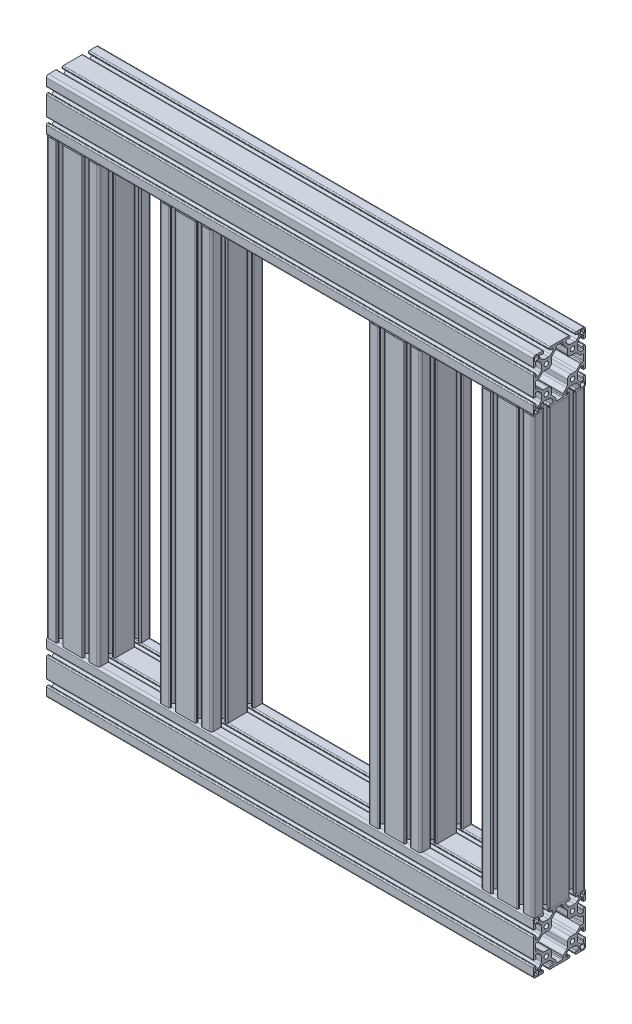
SolidWorks part; units mm, degrees
ref_plane "Front Plane" through (0, 0, 0) normal (0, 0, 1) x (1, 0, 0)
ref_plane "Top Plane" through (0, 0, 0) normal (0, 1, 0) x (1, 0, 0)
ref_plane "Right Plane" through (0, 0, 0) normal (1, 0, 0) x (0, 0, -1)
sketch "Sketch2" plane through (0, 0, 0) normal (0, 0, 1) x (1, 0, 0)
  line L0 (0, -372.5) -> (0, 372.5) construction
  line L1 (332.5, -372.5) -> (-332.5, -372.5)
  line L2 (332.5, -372.5) -> (332.5, 372.5)
  line L3 (332.5, 372.5) -> (-332.5, 372.5)
  line L4 (-332.5, -372.5) -> (-332.5, 372.5)
  line L5 (332.5, -372.5) -> (-332.5, 372.5) construction
  line L6 (332.5, 372.5) -> (-332.5, -372.5) construction
  line L7 (160, -372.5) -> (160, 372.5)
  line L8 (-160, -372.5) -> (-160, 372.5)
  point P0 (0, 0)
  dimension "D3" = 160
  dimension "D1" = 665
  dimension "D2" = 745
other "Aluminum 80X80(3)"
ref_plane "Plane2" through (332.5, 372.5, 0) normal (-1, 0, 0) x (0, -1, 0)
sketch "Sketch1" plane through (332.5, 372.5, 0) normal (-1, 0, 0) x (0, -1, 0)
  line L0 (33.22, -31.95) -> (37.715, -31.95)
  line L1 (38.35, -32.585) -> (38.35, -35.556)
  line L2 (35.556, -38.35) -> (32.585, -38.35)
  line L3 (31.95, -37.715) -> (31.95, -33.22)
  line L4 (-31.95, -33.22) -> (-31.95, -37.715)
  line L5 (-32.585, -38.35) -> (-35.556, -38.35)
  line L6 (-38.35, -35.556) -> (-38.35, -32.585)
  line L7 (-37.715, -31.95) -> (-33.22, -31.95)
  line L8 (-35.43, 5.41) -> (-32.7826, 5.41)
  line L9 (-31.8846, 5.782) -> (-26.7395, 10.9271)
  line L10 (-23.3809, 12.3182) -> (-17.0682, 12.3182)
  line L11 (-12.3182, 17.0682) -> (-12.3182, 23.3809)
  line L12 (-10.9271, 26.7395) -> (-5.782, 31.8846)
  line L13 (-5.41, 32.7826) -> (-5.41, 35.43)
  line L14 (-4.14, 36.7) -> (4.14, 36.7)
  line L15 (5.41, 35.43) -> (5.41, 32.7826)
  line L16 (5.782, 31.8846) -> (10.9271, 26.7395)
  line L17 (12.3182, 23.3809) -> (12.3182, 17.0682)
  line L18 (17.0682, 12.3182) -> (23.3809, 12.3182)
  line L19 (26.7395, 10.9271) -> (31.8846, 5.782)
  line L20 (32.7826, 5.41) -> (35.43, 5.41)
  line L21 (36.7, 4.14) -> (36.7, -4.14)
  line L22 (35.43, -5.41) -> (32.7826, -5.41)
  line L23 (31.8846, -5.782) -> (26.7395, -10.9271)
  line L24 (23.3809, -12.3182) -> (17.0682, -12.3182)
  line L25 (12.3182, -17.0682) -> (12.3182, -23.3809)
  line L26 (10.9271, -26.7395) -> (5.782, -31.8846)
  line L27 (5.41, -32.7826) -> (5.41, -35.43)
  line L28 (4.14, -36.7) -> (-4.14, -36.7)
  line L29 (-5.41, -35.43) -> (-5.41, -32.7826)
  line L30 (-5.782, -31.8846) -> (-10.9271, -26.7395)
  line L31 (-12.3182, -23.3809) -> (-12.3182, -17.0682)
  line L32 (-17.0682, -12.3182) -> (-23.3809, -12.3182)
  line L33 (-26.7395, -10.9271) -> (-31.8846, -5.782)
  line L34 (-32.7826, -5.41) -> (-35.43, -5.41)
  line L35 (-36.7, -4.14) -> (-36.7, 4.14)
  line L36 (-33.22, 31.95) -> (-37.715, 31.95)
  line L37 (-38.35, 32.585) -> (-38.35, 35.556)
  line L38 (-35.556, 38.35) -> (-32.585, 38.35)
  line L39 (-31.95, 37.715) -> (-31.95, 33.22)
  line L40 (31.95, 33.22) -> (31.95, 37.715)
  line L41 (32.585, 38.35) -> (35.556, 38.35)
  line L42 (38.35, 35.556) -> (38.35, 32.585)
  line L43 (37.715, 31.95) -> (33.22, 31.95)
  line L44 (-40, 14.37) -> (-40, -14.37)
  line L45 (-38.43, -15.94) -> (-37.51, -15.94)
  line L46 (-35.94, -14.37) -> (-35.94, -13.15)
  line L47 (-35.94, -13.15) -> (-36.7, -13.15)
  line L48 (-36.7, -13.15) -> (-36.7, -10.985)
  line L49 (-35.43, -9.715) -> (-32.9871, -9.715)
  line L50 (-32.3578, -9.9757) -> (-29.1593, -13.1742)
  line L51 (-27.6822, -16.6166) -> (-27.6822, -23.3834)
  line L52 (-29.1593, -26.8258) -> (-32.3578, -30.0243)
  line L53 (-32.9871, -30.285) -> (-35.43, -30.285)
  line L54 (-36.7, -29.015) -> (-36.7, -26.85)
  line L55 (-36.7, -26.85) -> (-35.94, -26.85)
  line L56 (-35.94, -26.85) -> (-35.94, -25.63)
  line L57 (-37.51, -24.06) -> (-38.43, -24.06)
  line L58 (-40, -25.63) -> (-40, -36.82)
  line L59 (-36.82, -40) -> (-25.63, -40)
  line L60 (-24.06, -38.43) -> (-24.06, -37.51)
  line L61 (-25.63, -35.94) -> (-26.85, -35.94)
  line L62 (-26.85, -35.94) -> (-26.85, -36.7)
  line L63 (-26.85, -36.7) -> (-29.015, -36.7)
  line L64 (-30.285, -35.43) -> (-30.285, -32.9871)
  line L65 (-30.0243, -32.3578) -> (-26.8258, -29.1593)
  line L66 (-23.3834, -27.6822) -> (-16.6166, -27.6822)
  line L67 (-13.1742, -29.1593) -> (-9.9757, -32.3578)
  line L68 (-9.715, -32.9871) -> (-9.715, -35.43)
  line L69 (-10.985, -36.7) -> (-13.15, -36.7)
  line L70 (-13.15, -36.7) -> (-13.15, -35.94)
  line L71 (-13.15, -35.94) -> (-14.37, -35.94)
  line L72 (-15.94, -37.51) -> (-15.94, -38.43)
  line L73 (-14.37, -40) -> (14.37, -40)
  line L74 (15.94, -38.43) -> (15.94, -37.51)
  line L75 (14.37, -35.94) -> (13.15, -35.94)
  line L76 (13.15, -35.94) -> (13.15, -36.7)
  line L77 (13.15, -36.7) -> (10.985, -36.7)
  line L78 (9.715, -35.43) -> (9.715, -32.9871)
  line L79 (9.9757, -32.3578) -> (13.1742, -29.1593)
  line L80 (16.6166, -27.6822) -> (23.3834, -27.6822)
  line L81 (26.8258, -29.1593) -> (30.0243, -32.3578)
  line L82 (30.285, -32.9871) -> (30.285, -35.43)
  line L83 (29.015, -36.7) -> (26.85, -36.7)
  line L84 (26.85, -36.7) -> (26.85, -35.94)
  line L85 (26.85, -35.94) -> (25.63, -35.94)
  line L86 (24.06, -37.51) -> (24.06, -38.43)
  line L87 (25.63, -40) -> (36.82, -40)
  line L88 (40, -36.82) -> (40, -25.63)
  line L89 (38.43, -24.06) -> (37.51, -24.06)
  line L90 (35.94, -25.63) -> (35.94, -26.85)
  line L91 (35.94, -26.85) -> (36.7, -26.85)
  line L92 (36.7, -26.85) -> (36.7, -29.015)
  line L93 (35.43, -30.285) -> (32.9871, -30.285)
  line L94 (32.3578, -30.0243) -> (29.1593, -26.8258)
  line L95 (27.6822, -23.3834) -> (27.6822, -16.6166)
  line L96 (29.1593, -13.1742) -> (32.3578, -9.9757)
  line L97 (32.9871, -9.715) -> (35.43, -9.715)
  line L98 (36.7, -10.985) -> (36.7, -13.15)
  line L99 (36.7, -13.15) -> (35.94, -13.15)
  line L100 (35.94, -13.15) -> (35.94, -14.37)
  line L101 (37.51, -15.94) -> (38.43, -15.94)
  line L102 (40, -14.37) -> (40, 14.37)
  line L103 (38.43, 15.94) -> (37.51, 15.94)
  line L104 (35.94, 14.37) -> (35.94, 13.15)
  line L105 (35.94, 13.15) -> (36.7, 13.15)
  line L106 (36.7, 13.15) -> (36.7, 10.985)
  line L107 (35.43, 9.715) -> (32.9871, 9.715)
  line L108 (32.3578, 9.9757) -> (29.1593, 13.1742)
  line L109 (27.6822, 16.6166) -> (27.6822, 23.3834)
  line L110 (29.1593, 26.8258) -> (32.3578, 30.0243)
  line L111 (32.9871, 30.285) -> (35.43, 30.285)
  line L112 (36.7, 29.015) -> (36.7, 26.85)
  line L113 (36.7, 26.85) -> (35.94, 26.85)
  line L114 (35.94, 26.85) -> (35.94, 25.63)
  line L115 (37.51, 24.06) -> (38.43, 24.06)
  line L116 (40, 25.63) -> (40, 36.82)
  line L117 (36.82, 40) -> (25.63, 40)
  line L118 (24.06, 38.43) -> (24.06, 37.51)
  line L119 (25.63, 35.94) -> (26.85, 35.94)
  line L120 (26.85, 35.94) -> (26.85, 36.7)
  line L121 (26.85, 36.7) -> (29.015, 36.7)
  line L122 (30.285, 35.43) -> (30.285, 32.9871)
  line L123 (30.0243, 32.3578) -> (26.8258, 29.1593)
  line L124 (23.3834, 27.6822) -> (16.6166, 27.6822)
  line L125 (13.1742, 29.1593) -> (9.9757, 32.3578)
  line L126 (9.715, 32.9871) -> (9.715, 35.43)
  line L127 (10.985, 36.7) -> (13.15, 36.7)
  line L128 (13.15, 36.7) -> (13.15, 35.94)
  line L129 (13.15, 35.94) -> (14.37, 35.94)
  line L130 (15.94, 37.51) -> (15.94, 38.43)
  line L131 (14.37, 40) -> (-14.37, 40)
  line L132 (-15.94, 38.43) -> (-15.94, 37.51)
  line L133 (-14.37, 35.94) -> (-13.15, 35.94)
  line L134 (-13.15, 35.94) -> (-13.15, 36.7)
  line L135 (-13.15, 36.7) -> (-10.985, 36.7)
  line L136 (-9.715, 35.43) -> (-9.715, 32.9871)
  line L137 (-9.9757, 32.3578) -> (-13.1742, 29.1593)
  line L138 (-16.6166, 27.6822) -> (-23.3834, 27.6822)
  line L139 (-26.8258, 29.1593) -> (-30.0243, 32.3578)
  line L140 (-30.285, 32.9871) -> (-30.285, 35.43)
  line L141 (-29.015, 36.7) -> (-26.85, 36.7)
  line L142 (-26.85, 36.7) -> (-26.85, 35.94)
  line L143 (-26.85, 35.94) -> (-25.63, 35.94)
  line L144 (-24.06, 37.51) -> (-24.06, 38.43)
  line L145 (-25.63, 40) -> (-36.82, 40)
  line L146 (-40, 36.82) -> (-40, 25.63)
  line L147 (-38.43, 24.06) -> (-37.51, 24.06)
  line L148 (-35.94, 25.63) -> (-35.94, 26.85)
  line L149 (-35.94, 26.85) -> (-36.7, 26.85)
  line L150 (-36.7, 26.85) -> (-36.7, 29.015)
  line L151 (-35.43, 30.285) -> (-32.9871, 30.285)
  line L152 (-32.3578, 30.0243) -> (-29.1593, 26.8258)
  line L153 (-27.6822, 23.3834) -> (-27.6822, 16.6166)
  line L154 (-29.1593, 13.1742) -> (-32.3578, 9.9757)
  line L155 (-32.9871, 9.715) -> (-35.43, 9.715)
  line L156 (-36.7, 10.985) -> (-36.7, 13.15)
  line L157 (-36.7, 13.15) -> (-35.94, 13.15)
  line L158 (-35.94, 13.15) -> (-35.94, 14.37)
  line L159 (-37.51, 15.94) -> (-38.43, 15.94)
  arc A0 (33.22, -31.95) -> (31.95, -33.22) centre (33.22, -33.22) ccw
  arc A1 (38.35, -32.585) -> (37.715, -31.95) centre (37.715, -32.585) ccw
  arc A2 (35.556, -38.35) -> (38.35, -35.556) centre (35.556, -35.556) ccw
  arc A3 (31.95, -37.715) -> (32.585, -38.35) centre (32.585, -37.715) ccw
  arc A4 (-31.95, -33.22) -> (-33.22, -31.95) centre (-33.22, -33.22) ccw
  arc A5 (-32.585, -38.35) -> (-31.95, -37.715) centre (-32.585, -37.715) ccw
  arc A6 (-38.35, -35.556) -> (-35.556, -38.35) centre (-35.556, -35.556) ccw
  arc A7 (-37.715, -31.95) -> (-38.35, -32.585) centre (-37.715, -32.585) ccw
  arc A8 (-35.43, 5.41) -> (-36.7, 4.14) centre (-35.43, 4.14) ccw
  arc A9 (-32.7826, 5.41) -> (-31.8846, 5.782) centre (-32.7826, 6.68) ccw
  arc A10 (-23.3809, 12.3182) -> (-26.7395, 10.9271) centre (-23.3809, 7.5684) ccw
  arc A11 (-17.0682, 12.3182) -> (-12.3182, 17.0682) centre (-17.0682, 17.0682) ccw
  arc A12 (-10.9271, 26.7395) -> (-12.3182, 23.3809) centre (-7.5684, 23.3809) ccw
  arc A13 (-5.782, 31.8846) -> (-5.41, 32.7826) centre (-6.68, 32.7826) ccw
  arc A14 (-4.14, 36.7) -> (-5.41, 35.43) centre (-4.14, 35.43) ccw
  arc A15 (5.41, 35.43) -> (4.14, 36.7) centre (4.14, 35.43) ccw
  arc A16 (5.41, 32.7826) -> (5.782, 31.8846) centre (6.68, 32.7826) ccw
  arc A17 (12.3182, 23.3809) -> (10.9271, 26.7395) centre (7.5684, 23.3809) ccw
  arc A18 (12.3182, 17.0682) -> (17.0682, 12.3182) centre (17.0682, 17.0682) ccw
  arc A19 (26.7395, 10.9271) -> (23.3809, 12.3182) centre (23.3809, 7.5684) ccw
  arc A20 (31.8846, 5.782) -> (32.7826, 5.41) centre (32.7826, 6.68) ccw
  arc A21 (36.7, 4.14) -> (35.43, 5.41) centre (35.43, 4.14) ccw
  arc A22 (35.43, -5.41) -> (36.7, -4.14) centre (35.43, -4.14) ccw
  arc A23 (32.7826, -5.41) -> (31.8846, -5.782) centre (32.7826, -6.68) ccw
  arc A24 (23.3809, -12.3182) -> (26.7395, -10.9271) centre (23.3809, -7.5684) ccw
  arc A25 (17.0682, -12.3182) -> (12.3182, -17.0682) centre (17.0682, -17.0682) ccw
  arc A26 (10.9271, -26.7395) -> (12.3182, -23.3809) centre (7.5684, -23.3809) ccw
  arc A27 (5.782, -31.8846) -> (5.41, -32.7826) centre (6.68, -32.7826) ccw
  arc A28 (4.14, -36.7) -> (5.41, -35.43) centre (4.14, -35.43) ccw
  arc A29 (-5.41, -35.43) -> (-4.14, -36.7) centre (-4.14, -35.43) ccw
  arc A30 (-5.41, -32.7826) -> (-5.782, -31.8846) centre (-6.68, -32.7826) ccw
  arc A31 (-12.3182, -23.3809) -> (-10.9271, -26.7395) centre (-7.5684, -23.3809) ccw
  arc A32 (-12.3182, -17.0682) -> (-17.0682, -12.3182) centre (-17.0682, -17.0682) ccw
  arc A33 (-26.7395, -10.9271) -> (-23.3809, -12.3182) centre (-23.3809, -7.5684) ccw
  arc A34 (-31.8846, -5.782) -> (-32.7826, -5.41) centre (-32.7826, -6.68) ccw
  arc A35 (-36.7, -4.14) -> (-35.43, -5.41) centre (-35.43, -4.14) ccw
  circle A36 centre (20, -20) radius 3.405
  circle A37 centre (-20, -20) radius 3.405
  circle A38 centre (-20, 20) radius 3.405
  circle A39 centre (20, 20) radius 3.405
  arc A40 (-33.22, 31.95) -> (-31.95, 33.22) centre (-33.22, 33.22) ccw
  arc A41 (-38.35, 32.585) -> (-37.715, 31.95) centre (-37.715, 32.585) ccw
  arc A42 (-35.556, 38.35) -> (-38.35, 35.556) centre (-35.556, 35.556) ccw
  arc A43 (-31.95, 37.715) -> (-32.585, 38.35) centre (-32.585, 37.715) ccw
  arc A44 (31.95, 33.22) -> (33.22, 31.95) centre (33.22, 33.22) ccw
  arc A45 (32.585, 38.35) -> (31.95, 37.715) centre (32.585, 37.715) ccw
  arc A46 (38.35, 35.556) -> (35.556, 38.35) centre (35.556, 35.556) ccw
  arc A47 (37.715, 31.95) -> (38.35, 32.585) centre (37.715, 32.585) ccw
  arc A48 (-38.43, 15.94) -> (-40, 14.37) centre (-38.43, 14.37) ccw
  arc A49 (-40, -14.37) -> (-38.43, -15.94) centre (-38.43, -14.37) ccw
  arc A50 (-37.51, -15.94) -> (-35.94, -14.37) centre (-37.51, -14.37) ccw
  arc A51 (-35.43, -9.715) -> (-36.7, -10.985) centre (-35.43, -10.985) ccw
  arc A52 (-32.3578, -9.9757) -> (-32.9871, -9.715) centre (-32.9871, -10.605) ccw
  arc A53 (-27.6822, -16.6166) -> (-29.1593, -13.1742) centre (-32.4322, -16.6166) ccw
  arc A54 (-29.1593, -26.8258) -> (-27.6822, -23.3834) centre (-32.4322, -23.3834) ccw
  arc A55 (-32.9871, -30.285) -> (-32.3578, -30.0243) centre (-32.9871, -29.395) ccw
  arc A56 (-36.7, -29.015) -> (-35.43, -30.285) centre (-35.43, -29.015) ccw
  arc A57 (-35.94, -25.63) -> (-37.51, -24.06) centre (-37.51, -25.63) ccw
  arc A58 (-38.43, -24.06) -> (-40, -25.63) centre (-38.43, -25.63) ccw
  arc A59 (-40, -36.82) -> (-36.82, -40) centre (-36.82, -36.82) ccw
  arc A60 (-25.63, -40) -> (-24.06, -38.43) centre (-25.63, -38.43) ccw
  arc A61 (-24.06, -37.51) -> (-25.63, -35.94) centre (-25.63, -37.51) ccw
  arc A62 (-30.285, -35.43) -> (-29.015, -36.7) centre (-29.015, -35.43) ccw
  arc A63 (-30.0243, -32.3578) -> (-30.285, -32.9871) centre (-29.395, -32.9871) ccw
  arc A64 (-23.3834, -27.6822) -> (-26.8258, -29.1593) centre (-23.3834, -32.4322) ccw
  arc A65 (-13.1742, -29.1593) -> (-16.6166, -27.6822) centre (-16.6166, -32.4322) ccw
  arc A66 (-9.715, -32.9871) -> (-9.9757, -32.3578) centre (-10.605, -32.9871) ccw
  arc A67 (-10.985, -36.7) -> (-9.715, -35.43) centre (-10.985, -35.43) ccw
  arc A68 (-14.37, -35.94) -> (-15.94, -37.51) centre (-14.37, -37.51) ccw
  arc A69 (-15.94, -38.43) -> (-14.37, -40) centre (-14.37, -38.43) ccw
  arc A70 (14.37, -40) -> (15.94, -38.43) centre (14.37, -38.43) ccw
  arc A71 (15.94, -37.51) -> (14.37, -35.94) centre (14.37, -37.51) ccw
  arc A72 (9.715, -35.43) -> (10.985, -36.7) centre (10.985, -35.43) ccw
  arc A73 (9.9757, -32.3578) -> (9.715, -32.9871) centre (10.605, -32.9871) ccw
  arc A74 (16.6166, -27.6822) -> (13.1742, -29.1593) centre (16.6166, -32.4322) ccw
  arc A75 (26.8258, -29.1593) -> (23.3834, -27.6822) centre (23.3834, -32.4322) ccw
  arc A76 (30.285, -32.9871) -> (30.0243, -32.3578) centre (29.395, -32.9871) ccw
  arc A77 (29.015, -36.7) -> (30.285, -35.43) centre (29.015, -35.43) ccw
  arc A78 (25.63, -35.94) -> (24.06, -37.51) centre (25.63, -37.51) ccw
  arc A79 (24.06, -38.43) -> (25.63, -40) centre (25.63, -38.43) ccw
  arc A80 (36.82, -40) -> (40, -36.82) centre (36.82, -36.82) ccw
  arc A81 (40, -25.63) -> (38.43, -24.06) centre (38.43, -25.63) ccw
  arc A82 (37.51, -24.06) -> (35.94, -25.63) centre (37.51, -25.63) ccw
  arc A83 (35.43, -30.285) -> (36.7, -29.015) centre (35.43, -29.015) ccw
  arc A84 (32.3578, -30.0243) -> (32.9871, -30.285) centre (32.9871, -29.395) ccw
  arc A85 (27.6822, -23.3834) -> (29.1593, -26.8258) centre (32.4322, -23.3834) ccw
  arc A86 (29.1593, -13.1742) -> (27.6822, -16.6166) centre (32.4322, -16.6166) ccw
  arc A87 (32.9871, -9.715) -> (32.3578, -9.9757) centre (32.9871, -10.605) ccw
  arc A88 (36.7, -10.985) -> (35.43, -9.715) centre (35.43, -10.985) ccw
  arc A89 (35.94, -14.37) -> (37.51, -15.94) centre (37.51, -14.37) ccw
  arc A90 (38.43, -15.94) -> (40, -14.37) centre (38.43, -14.37) ccw
  arc A91 (40, 14.37) -> (38.43, 15.94) centre (38.43, 14.37) ccw
  arc A92 (37.51, 15.94) -> (35.94, 14.37) centre (37.51, 14.37) ccw
  arc A93 (35.43, 9.715) -> (36.7, 10.985) centre (35.43, 10.985) ccw
  arc A94 (32.3578, 9.9757) -> (32.9871, 9.715) centre (32.9871, 10.605) ccw
  arc A95 (27.6822, 16.6166) -> (29.1593, 13.1742) centre (32.4322, 16.6166) ccw
  arc A96 (29.1593, 26.8258) -> (27.6822, 23.3834) centre (32.4322, 23.3834) ccw
  arc A97 (32.9871, 30.285) -> (32.3578, 30.0243) centre (32.9871, 29.395) ccw
  arc A98 (36.7, 29.015) -> (35.43, 30.285) centre (35.43, 29.015) ccw
  arc A99 (35.94, 25.63) -> (37.51, 24.06) centre (37.51, 25.63) ccw
  arc A100 (38.43, 24.06) -> (40, 25.63) centre (38.43, 25.63) ccw
  arc A101 (40, 36.82) -> (36.82, 40) centre (36.82, 36.82) ccw
  arc A102 (25.63, 40) -> (24.06, 38.43) centre (25.63, 38.43) ccw
  arc A103 (24.06, 37.51) -> (25.63, 35.94) centre (25.63, 37.51) ccw
  arc A104 (30.285, 35.43) -> (29.015, 36.7) centre (29.015, 35.43) ccw
  arc A105 (30.0243, 32.3578) -> (30.285, 32.9871) centre (29.395, 32.9871) ccw
  arc A106 (23.3834, 27.6822) -> (26.8258, 29.1593) centre (23.3834, 32.4322) ccw
  arc A107 (13.1742, 29.1593) -> (16.6166, 27.6822) centre (16.6166, 32.4322) ccw
  arc A108 (9.715, 32.9871) -> (9.9757, 32.3578) centre (10.605, 32.9871) ccw
  arc A109 (10.985, 36.7) -> (9.715, 35.43) centre (10.985, 35.43) ccw
  arc A110 (14.37, 35.94) -> (15.94, 37.51) centre (14.37, 37.51) ccw
  arc A111 (15.94, 38.43) -> (14.37, 40) centre (14.37, 38.43) ccw
  arc A112 (-14.37, 40) -> (-15.94, 38.43) centre (-14.37, 38.43) ccw
  arc A113 (-15.94, 37.51) -> (-14.37, 35.94) centre (-14.37, 37.51) ccw
  arc A114 (-9.715, 35.43) -> (-10.985, 36.7) centre (-10.985, 35.43) ccw
  arc A115 (-9.9757, 32.3578) -> (-9.715, 32.9871) centre (-10.605, 32.9871) ccw
  arc A116 (-16.6166, 27.6822) -> (-13.1742, 29.1593) centre (-16.6166, 32.4322) ccw
  arc A117 (-26.8258, 29.1593) -> (-23.3834, 27.6822) centre (-23.3834, 32.4322) ccw
  arc A118 (-30.285, 32.9871) -> (-30.0243, 32.3578) centre (-29.395, 32.9871) ccw
  arc A119 (-29.015, 36.7) -> (-30.285, 35.43) centre (-29.015, 35.43) ccw
  arc A120 (-25.63, 35.94) -> (-24.06, 37.51) centre (-25.63, 37.51) ccw
  arc A121 (-24.06, 38.43) -> (-25.63, 40) centre (-25.63, 38.43) ccw
  arc A122 (-36.82, 40) -> (-40, 36.82) centre (-36.82, 36.82) ccw
  arc A123 (-40, 25.63) -> (-38.43, 24.06) centre (-38.43, 25.63) ccw
  arc A124 (-37.51, 24.06) -> (-35.94, 25.63) centre (-37.51, 25.63) ccw
  arc A125 (-35.43, 30.285) -> (-36.7, 29.015) centre (-35.43, 29.015) ccw
  arc A126 (-32.3578, 30.0243) -> (-32.9871, 30.285) centre (-32.9871, 29.395) ccw
  arc A127 (-27.6822, 23.3834) -> (-29.1593, 26.8258) centre (-32.4322, 23.3834) ccw
  arc A128 (-29.1593, 13.1742) -> (-27.6822, 16.6166) centre (-32.4322, 16.6166) ccw
  arc A129 (-32.9871, 9.715) -> (-32.3578, 9.9757) centre (-32.9871, 10.605) ccw
  arc A130 (-36.7, 10.985) -> (-35.43, 9.715) centre (-35.43, 10.985) ccw
  arc A131 (-35.94, 14.37) -> (-37.51, 15.94) centre (-37.51, 14.37) ccw
  point P0 (0, 0)
equation "\"D2@Sketch2\"=665+80"
